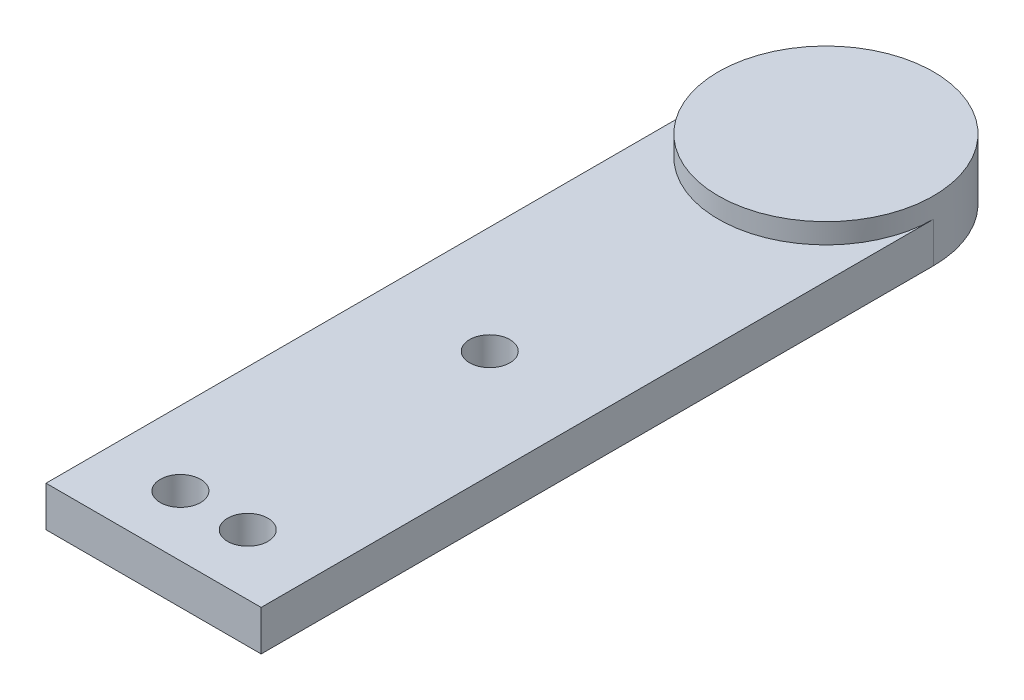
SolidWorks part; units mm, degrees
ref_plane "Plano frontal" through (0, 0, 0) normal (0, 0, 1) x (1, 0, 0)
ref_plane "Plano superior" through (0, 0, 0) normal (0, 1, 0) x (1, 0, 0)
ref_plane "Plano direito" through (0, 0, 0) normal (1, 0, 0) x (0, 0, -1)
sketch "Sketch1" plane through (0, 0, 0) normal (0, 1, 0) x (1, 0, 0)
  circle A0 centre (0, 0) radius 8
  dimension "D1" = 16
extrude "Boss-Extrude1" add sketch "Sketch1" against normal blind 1.5 and the other way blind 3
sketch "Sketch2" plane through (0, 0, 0) normal (0, 1, 0) x (1, 0, 0)
  line L1 (-8, 0) -> (8, 0)
  line L2 (-8, 0) -> (-8, -50)
  line L3 (-8, -50) -> (8, -50)
  line L4 (8, 0) -> (8, -50)
  circle A1 centre (0, 0) radius 8 construction
  dimension "D1" = 50
extrude "Boss-Extrude2" add sketch "Sketch2" along normal mid plane 3
sketch "Sketch3" plane through (0, -1.5, 0) normal (0, -1, 0) x (-1, 0, 0)
  line L1 (8, -50) -> (-8, -50) construction
  circle A0 centre (2.5031, -45.5) radius 1.5
  circle A1 centre (-2.5031, -45.5) radius 1.5
  dimension "D4" = 3
  dimension "D5" = 3
  dimension "D1" = 2.5031
  dimension "D2" = 2.5031
  dimension "D3" = 4.5
extrude "Cut-Extrude1" cut sketch "Sketch3" against normal up to next
sketch "Sketch4" plane through (0, -1.5, 0) normal (0, -1, 0) x (-1, 0, 0)
  line L0 (-3.3, 0) -> (3.3, 0)
  circle A0 centre (0, 0) radius 3.3
  dimension "D1" = 6.6
revolve "Cut-Revolve21" cut sketch "Sketch4" angle 360 about L0 region at (0, -1.5, 1.4006)
sketch "Sketch5" plane through (0, 1.5, 0) normal (0, 1, 0) x (1, 0, 0)
  line L3 (-8, 0) -> (-8, -50)
  line L4 (-8, -50) -> (8, -50)
  line L5 (8, -50) -> (8, 0)
  line L6 (-8, 0) -> (-8, -50)
  line L7 (-8, -50) -> (8, -50)
  line L8 (8, -50) -> (8, 0)
  circle A0 centre (0, -25) radius 1.5
  arc A1 (-8, 0) -> (8, 0) centre (0, 0) ccw
  arc A2 (-8, 0) -> (8, 0) centre (0, 0) ccw
  dimension "D4" = 3
  dimension "D2" = 50
  dimension "D3" = 25
extrude "Cut-Extrude3" cut sketch "Sketch5" against normal up to next contours A0
equation "\"D2@Sketch3\"=\"D1@Sketch3\""
equation "\"D5@Sketch3\"=\"D4@Sketch3\""
equation "\"D3@Sketch5\"=\"D2@Sketch5\"/2"
